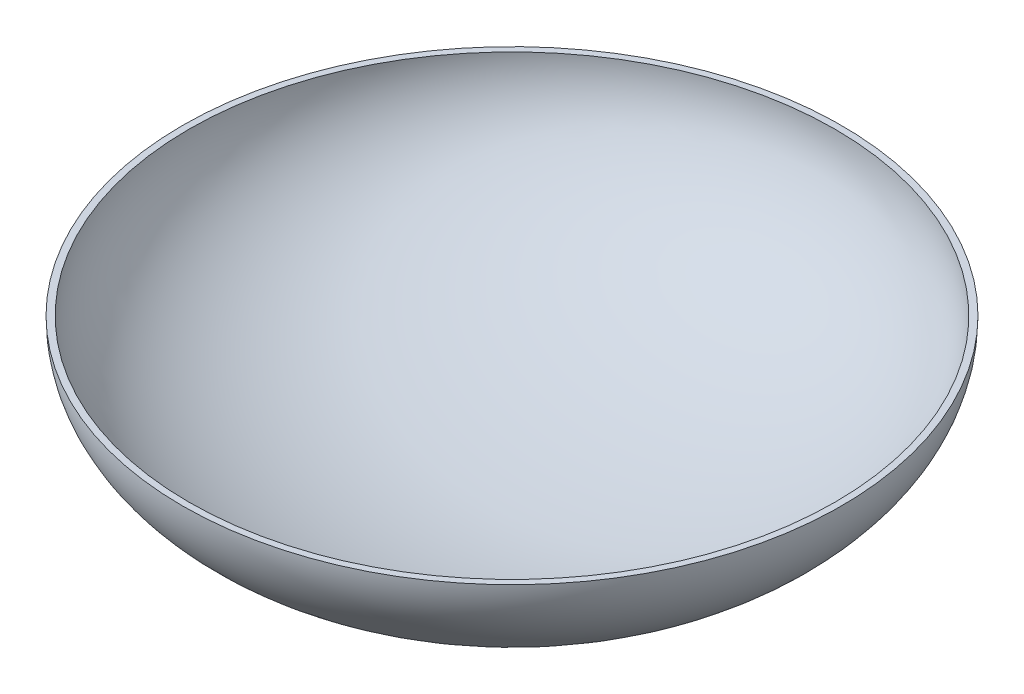
SolidWorks part; units mm, degrees
ref_plane "Front Plane" through (0, 0, 0) normal (0, 0, 1) x (1, 0, 0)
ref_plane "Top Plane" through (0, 0, 0) normal (0, 1, 0) x (1, 0, 0)
ref_plane "Right Plane" through (0, 0, 0) normal (1, 0, 0) x (0, 0, -1)
sketch "Sketch1" plane through (0, 0, 0) normal (0, 0, 1) x (1, 0, 0)
  line L0 (0, -1.8677) -> (-127, -1.8677) construction
  line L1 (-127, -1.8677) -> (-129.54, -1.8677)
  line L2 (0, -65.3677) -> (0, -1.8677) construction
  line L3 (0, -65.3677) -> (0, -67.9077)
  ellipse E0 centre (0, -1.8677) end of major axis (127, -1.8677) minor radius 63.5 (-127, -1.8677) -> (0, -65.3677) ccw
  ellipse E1 centre (0, -1.8677) end of major axis (129.54, -1.8677) minor radius 66.04 (-129.54, -1.8677) -> (0, -67.9077) ccw
  dimension "D1" = 127
  dimension "D2" = 63.5
  dimension "D3" = 2.54
  dimension "D4" = 2.54
revolve "Revolve1" add sketch "Sketch1" angle 360 about L3
